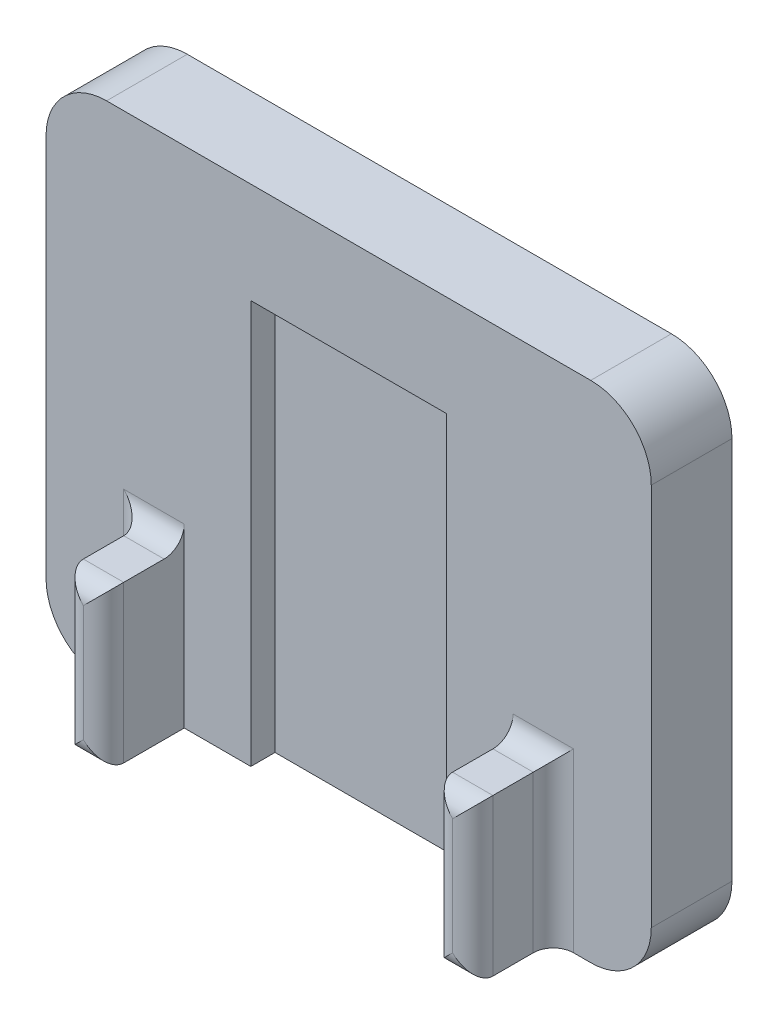
SolidWorks part; units mm, degrees
ref_plane "Front Plane" through (0, 0, 0) normal (0, 0, 1) x (1, 0, 0)
ref_plane "Top Plane" through (0, 0, 0) normal (0, 1, 0) x (1, 0, 0)
ref_plane "Right Plane" through (0, 0, 0) normal (1, 0, 0) x (0, 0, -1)
sketch "Sketch1" plane through (0, 0, 0) normal (0, 0, 1) x (1, 0, 0)
  line L1 (0, 0) -> (30, 0)
  line L2 (0, 0) -> (0, 25)
  line L3 (0, 25) -> (30, 25)
  line L4 (30, 0) -> (30, 25)
  dimension "D1" = 30
  dimension "D2" = 25
extrude "Boss-Extrude1" add sketch "Sketch1" along normal blind 4
sketch "Sketch3" plane through (0, 0, 4) normal (0, 0, 1) x (1, 0, 0)
  line L0 (0, 0) -> (30, 0) construction
  line L1 (19.85, 0) -> (10.15, 0)
  line L2 (19.85, 0) -> (19.85, 20)
  line L3 (19.85, 20) -> (10.15, 20)
  line L4 (10.15, 0) -> (10.15, 20)
  line L7 (0, 20) -> (30, 20) construction
  line L8 (0, 25) -> (0, 0) construction
  line L9 (30, 0) -> (30, 25) construction
  point P7 (15, 20)
  dimension "D1" = 20
  dimension "D2" = 9.7
extrude "Cut-Extrude1" cut sketch "Sketch3" against normal blind 1.2
fillet "Fillet1" radius 3 4 edges at (0, 25, 2) (0, 0, 2) (30, 25, 2) (30, 0, 2)
sketch "Sketch4" plane through (0, 0, 4) normal (0, 0, 1) x (1, 0, 0)
  line L1 (23.15, 0) -> (25.15, 0)
  line L2 (23.15, 0) -> (23.15, 7.7551)
  line L3 (23.15, 7.7551) -> (25.15, 7.7551)
  line L4 (25.15, 0) -> (25.15, 7.7551)
  line L5 (15, 25) -> (15, 0) construction
  line L6 (27, 25) -> (3, 25) construction
  line L7 (19.85, 0) -> (27, 0) construction
  line L8 (6.85, 0) -> (4.85, 0)
  line L9 (4.85, 0) -> (4.85, 7.7551)
  line L10 (6.85, 7.7551) -> (4.85, 7.7551)
  line L11 (6.85, 0) -> (6.85, 7.7551)
  dimension "D1" = 8.15
  dimension "D2" = 2
extrude "Boss-Extrude2" add sketch "Sketch4" along normal blind 4
fillet "Fillet2" radius 1 12 edges at (5.85, 0, 8) (4.85, 3.8775, 8) (5.85, 7.7551, 8) (6.85, 3.8775, 8) (24.15, 7.7551, 8) (25.15, 3.8775, 8) (24.15, 0, 8) (23.15, 3.8775, 8) (25.15, 3.8775, 4) (24.15, 7.7551, 4) (5.85, 7.7551, 4) (4.85, 3.8775, 4)
